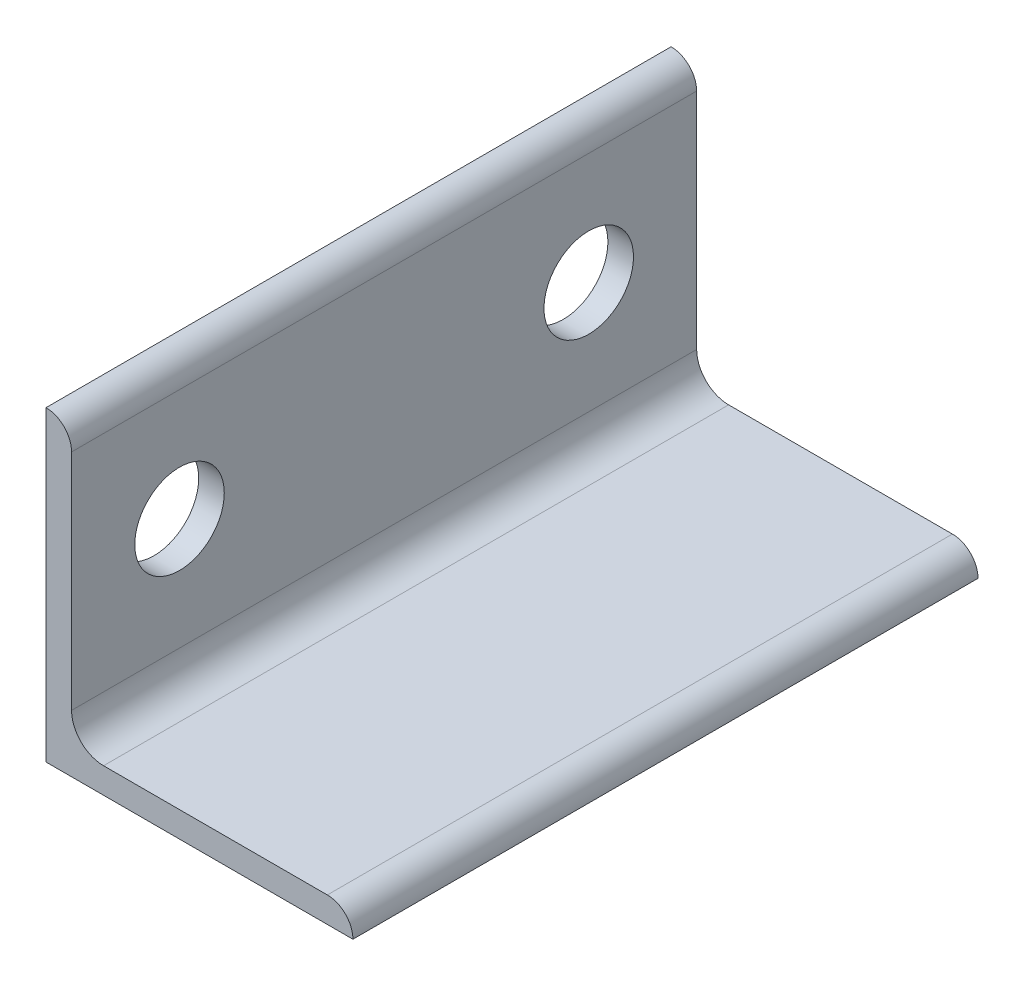
SolidWorks part; units mm, degrees
ref_plane "Front Plane" through (0, 0, 0) normal (0, 0, 1) x (1, 0, 0)
ref_plane "Top Plane" through (0, 0, 0) normal (0, 1, 0) x (1, 0, 0)
ref_plane "Right Plane" through (0, 0, 0) normal (1, 0, 0) x (0, 0, -1)
sketch "Sketch1" plane through (0, 0, 0) normal (0, 0, 1) x (1, 0, 0)
  line L0 (-47.625, 0) -> (-47.625, 76.2)
  line L2 (-47.625, 0) -> (28.575, 0)
  line L3 (22.225, 6.35) -> (-33.3375, 6.35)
  line L4 (-41.275, 69.85) -> (-41.275, 14.2875)
  arc A0 (-41.275, 69.85) -> (-47.625, 76.2) centre (-47.625, 69.85) ccw
  arc A1 (-41.275, 14.2875) -> (-33.3375, 6.35) centre (-33.3375, 14.2875) ccw
  arc A2 (22.225, 6.35) -> (28.575, 0) centre (22.225, 0) cw
  dimension "D4" = 6.35
extrude "Boss-Extrude1" add sketch "Sketch1" against normal offset from surface (155.194 mm away) 19.05
sketch "Sketch2" plane through (-41.275, 0, 0) normal (1, 0, 0) x (0, 0, -1)
  line L0 (77.597, 69.85) -> (77.597, 14.2875) construction
  line L1 (155.194, 69.85) -> (0, 69.85) construction
  line L2 (155.194, 14.2875) -> (0, 14.2875) construction
  line L3 (128.397, 42.0688) -> (26.797, 42.0687) construction
  circle A0 centre (128.397, 42.0688) radius 11.1125
  circle A1 centre (26.797, 42.0687) radius 11.1125
  point P8 (77.597, 42.0687)
  dimension "D1" = 22.225
  dimension "D2" = 101.6
extrude "Cut-Extrude1" cut sketch "Sketch2" against normal up to next
sketch "Sketch3" plane through (0, 6.35, 0) normal (0, 1, 0) x (1, 0, 0)
  line L0 (-33.3375, 77.597) -> (22.225, 77.597) construction
  line L1 (-33.3375, 155.194) -> (-33.3375, 0) construction
  line L2 (22.225, 155.194) -> (22.225, 0) construction
  line L3 (-5.5563, 128.397) -> (-5.5563, 26.797) construction
  line L4 (-5.5563, 128.397) -> (-41.275, 128.397) construction
  line L5 (-41.275, 117.2845) -> (-41.275, 139.5095) construction
  circle A0 centre (-5.5563, 128.397) radius 11.1125
  circle A1 centre (-5.5563, 26.797) radius 11.1125
  point P8 (-5.5563, 77.597)
  dimension "D1" = 22.225
